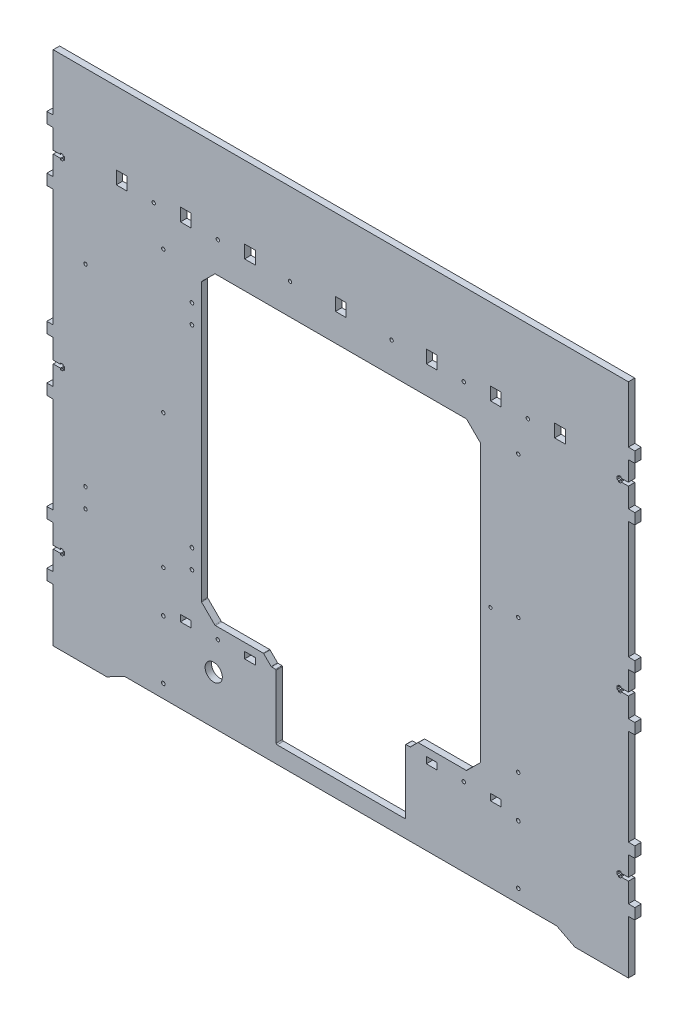
SolidWorks part; units mm, degrees
material "Клен"
ref_plane "Front" through (0, 0, 0) normal (0, 0, 1) x (1, 0, 0)
ref_plane "Top" through (0, 0, 0) normal (0, 1, 0) x (1, 0, 0)
ref_plane "Right" through (0, 0, 0) normal (1, 0, 0) x (0, 0, -1)
sketch "Эскиз2" plane through (0, 0, 0) normal (0, 0, 1) x (1, 0, 0)
  line L0 (400.4244, 482.0072) -> (-19.6784, 482.0072) construction
  line L1 (308.1919, 504.8221) -> (308.1919, 0) construction
  line L2 (39.1919, 504.8221) -> (39.1919, 18.7975) construction
  line L3 (33.1919, 504.8221) -> (33.1919, 18.7975) construction
  line L4 (228.1919, 149.8356) -> (228.1919, 102.1072) construction
  line L5 (168.1919, 135.3857) -> (168.1919, 108.8729) construction
  line L6 (193.1919, 141.9072) -> (193.1919, 108.8729) construction
  line L7 (260.6919, 457.1072) -> (260.6919, 439.2572) construction
  line L8 (228.1919, 461.9072) -> (228.1919, 439.2572) construction
  line L13 (193.1919, 457.1072) -> (193.1919, 440.4572) construction
  line L19 (39.1919, 472.1072) -> (33.1919, 472.0072)
  line L20 (33.1919, 472.0072) -> (33.1919, 462.0072)
  line L21 (33.1919, 462.0072) -> (39.1919, 461.9072)
  line L22 (39.1919, 461.9072) -> (39.1919, 443.5572)
  line L23 (39.1919, 443.5572) -> (45.9919, 443.5572)
  line L24 (45.9919, 443.5572) -> (45.9919, 444.7572)
  line L25 (45.9919, 444.7572) -> (48.1919, 444.7572)
  line L26 (48.1919, 444.7572) -> (48.1919, 443.5572)
  line L27 (48.1919, 443.5572) -> (49.6919, 443.5572)
  line L28 (49.6919, 443.5572) -> (49.6919, 440.4572)
  line L29 (49.6919, 440.4572) -> (48.1919, 440.4572)
  line L30 (48.1919, 440.4572) -> (48.1919, 439.2572)
  line L31 (48.1919, 439.2572) -> (45.9919, 439.2572)
  line L32 (45.9919, 439.2572) -> (45.9919, 440.4572)
  line L33 (45.9919, 440.4572) -> (39.1919, 440.4572)
  line L34 (39.1919, 440.4572) -> (39.1919, 422.1072)
  line L35 (39.1919, 422.1072) -> (33.1919, 422.0072)
  line L36 (33.1919, 422.0072) -> (33.1919, 412.0072)
  line L37 (33.1919, 412.0072) -> (39.1919, 411.9072)
  line L38 (39.1919, 411.9072) -> (39.1919, 302.1072)
  line L39 (39.1919, 302.1072) -> (33.1919, 302.0072)
  line L40 (33.1919, 302.0072) -> (33.1919, 292.0072)
  line L41 (33.1919, 292.0072) -> (39.1919, 291.9072)
  line L42 (39.1919, 291.9072) -> (39.1919, 273.5572)
  line L43 (39.1919, 273.5572) -> (45.9919, 273.5572)
  line L44 (45.9919, 273.5572) -> (45.9919, 274.7572)
  line L45 (45.9919, 274.7572) -> (48.1919, 274.7572)
  line L46 (48.1919, 274.7572) -> (48.1919, 273.5572)
  line L47 (48.1919, 273.5572) -> (49.6919, 273.5572)
  line L48 (49.6919, 273.5572) -> (49.6919, 270.4572)
  line L49 (49.6919, 270.4572) -> (48.1919, 270.4572)
  line L50 (48.1919, 270.4572) -> (48.1919, 269.2572)
  line L51 (48.1919, 269.2572) -> (45.9919, 269.2572)
  line L52 (45.9919, 269.2572) -> (45.9919, 270.4572)
  line L53 (45.9919, 270.4572) -> (39.1919, 270.4572)
  line L54 (39.1919, 270.4572) -> (39.1919, 252.1072)
  line L55 (39.1919, 252.1072) -> (33.1919, 252.0072)
  line L56 (33.1919, 252.0072) -> (33.1919, 242.0072)
  line L57 (33.1919, 242.0072) -> (39.1919, 241.9072)
  line L58 (39.1919, 241.9072) -> (39.1919, 152.1072)
  line L59 (39.1919, 152.1072) -> (33.1919, 152.0072)
  line L60 (33.1919, 152.0072) -> (33.1919, 142.0072)
  line L61 (33.1919, 142.0072) -> (39.1919, 141.9072)
  line L62 (39.1919, 141.9072) -> (39.1919, 123.5572)
  line L63 (39.1919, 123.5572) -> (45.9919, 123.5572)
  line L64 (45.9919, 123.5572) -> (45.9919, 124.7572)
  line L65 (45.9919, 124.7572) -> (48.1919, 124.7572)
  line L66 (48.1919, 124.7572) -> (48.1919, 123.5572)
  line L67 (48.1919, 123.5572) -> (49.6919, 123.5572)
  line L68 (49.6919, 123.5572) -> (49.6919, 120.4572)
  line L69 (49.6919, 120.4572) -> (48.1919, 120.4572)
  line L70 (48.1919, 120.4572) -> (48.1919, 119.2572)
  line L71 (48.1919, 119.2572) -> (45.9919, 119.2572)
  line L72 (45.9919, 119.2572) -> (45.9919, 120.4572)
  line L73 (45.9919, 120.4572) -> (39.1919, 120.4572)
  line L74 (39.1919, 120.4572) -> (39.1919, 102.1072)
  line L75 (39.1919, 102.1072) -> (33.1919, 102.0072)
  line L76 (33.1919, 102.0072) -> (33.1919, 92.0072)
  line L77 (33.1919, 92.0072) -> (39.1919, 91.9072)
  line L78 (39.1919, 91.9072) -> (39.1919, 42.0072)
  line L79 (39.1919, 42.0072) -> (89.1919, 42.0072)
  line L80 (89.1919, 42.0072) -> (106.1919, 50.7072)
  line L81 (106.1919, 50.7072) -> (510.1919, 50.7072)
  line L82 (313.1919, 457.1072) -> (303.1919, 457.1072)
  line L83 (168.1919, 461.9072) -> (168.1919, 439.2572) construction
  line L84 (303.1919, 457.1072) -> (303.1919, 445.0072)
  line L85 (303.1919, 445.0072) -> (313.1919, 445.0072)
  line L87 (169.3644, 152.1072) -> (169.3644, 392.271) construction
  line L88 (218.1919, 127.1049) -> (228.1919, 127.1049)
  line L89 (218.1919, 127.1049) -> (218.1919, 121.0049)
  line L90 (218.1919, 121.0049) -> (228.1919, 121.0049)
  line L91 (228.1919, 127.1049) -> (228.1919, 121.0049)
  line L92 (158.1919, 127.1049) -> (168.1919, 127.1049)
  line L93 (158.1919, 127.1049) -> (158.1919, 121.0049)
  line L94 (158.1919, 121.0049) -> (168.1919, 121.0049)
  line L95 (168.1919, 127.1049) -> (168.1919, 121.0049)
  line L96 (158.1919, 457.1072) -> (168.1919, 457.1072)
  line L97 (158.1919, 457.1072) -> (158.1919, 445.0072)
  line L98 (158.1919, 445.0072) -> (168.1919, 445.0072)
  line L99 (168.1919, 457.1072) -> (168.1919, 445.0072)
  line L100 (218.1919, 457.1072) -> (228.1919, 457.1072)
  line L101 (218.1919, 457.1072) -> (218.1919, 445.0072)
  line L102 (218.1919, 445.0072) -> (228.1919, 445.0072)
  line L103 (228.1919, 457.1072) -> (228.1919, 445.0072)
  line L105 (367.6919, 66.6049) -> (248.6919, 66.6049)
  line L107 (247.6919, 67.6049) -> (247.6919, 126.6049)
  line L108 (247.1919, 127.1049) -> (243.399, 127.1049)
  line L109 (239.5515, 130.7453) -> (243.0455, 127.2514)
  line L111 (239.5515, 130.7453) -> (236.0575, 134.2393)
  line L112 (213.3308, 134.3857) -> (235.704, 134.3857)
  line L113 (108.1919, 457.1072) -> (108.1919, 445.0072)
  line L114 (213.3308, 134.3857) -> (190.9576, 134.3857)
  line L115 (184.1064, 140.7795) -> (190.253, 134.6761)
  line L116 (98.1919, 445.0072) -> (108.1919, 445.0072)
  line L117 (184.1064, 140.7795) -> (177.9598, 146.8828)
  line L118 (177.6644, 169.7011) -> (177.6644, 147.5924)
  line L119 (98.1919, 457.1072) -> (108.1919, 457.1072)
  line L120 (177.6644, 169.7011) -> (177.6644, 405.9627)
  line L121 (184.1064, 412.7756) -> (177.9598, 406.6723)
  line L122 (98.1919, 457.1072) -> (98.1919, 445.0072)
  line L123 (184.1064, 412.7756) -> (190.253, 418.8789)
  line L124 (308.1379, 419.1693) -> (190.9576, 419.1693)
  line L125 (518.1919, 457.1072) -> (508.1919, 457.1072)
  line L126 (308.2459, 419.1693) -> (425.4263, 419.1693)
  line L127 (432.2775, 412.7756) -> (426.1309, 418.8789)
  line L128 (432.2775, 412.7756) -> (438.4241, 406.6723)
  line L129 (438.7195, 169.7011) -> (438.7195, 405.9627)
  line L130 (438.7195, 169.7011) -> (438.7195, 147.5924)
  line L131 (432.2775, 140.7795) -> (438.4241, 146.8828)
  line L132 (432.2775, 140.7795) -> (426.1309, 134.6761)
  line L133 (403.0531, 134.3857) -> (425.4263, 134.3857)
  line L134 (403.0531, 134.3857) -> (380.6799, 134.3857)
  line L135 (376.8323, 130.7453) -> (380.3263, 134.2393)
  line L136 (376.8323, 130.7453) -> (373.3384, 127.2514)
  line L137 (369.1919, 127.1049) -> (372.9848, 127.1049)
  line L138 (368.6919, 67.6049) -> (368.6919, 126.6049)
  line L139 (388.1919, 457.1072) -> (388.1919, 445.0072)
  line L140 (398.1919, 445.0072) -> (388.1919, 445.0072)
  line L141 (398.1919, 457.1072) -> (398.1919, 445.0072)
  line L142 (398.1919, 457.1072) -> (388.1919, 457.1072)
  line L143 (448.1919, 457.1072) -> (448.1919, 445.0072)
  line L144 (458.1919, 445.0072) -> (448.1919, 445.0072)
  line L145 (458.1919, 457.1072) -> (458.1919, 445.0072)
  line L146 (458.1919, 457.1072) -> (448.1919, 457.1072)
  line L147 (448.1919, 127.1049) -> (448.1919, 121.0049)
  line L148 (458.1919, 121.0049) -> (448.1919, 121.0049)
  line L149 (458.1919, 127.1049) -> (458.1919, 121.0049)
  line L150 (458.1919, 127.1049) -> (448.1919, 127.1049)
  line L151 (388.1919, 127.1049) -> (388.1919, 121.0049)
  line L152 (398.1919, 121.0049) -> (388.1919, 121.0049)
  line L153 (398.1919, 127.1049) -> (398.1919, 121.0049)
  line L154 (398.1919, 127.1049) -> (388.1919, 127.1049)
  line L155 (313.1919, 457.1072) -> (313.1919, 445.0072)
  line L156 (527.1919, 42.0072) -> (510.1919, 50.7072)
  line L157 (577.1919, 42.0072) -> (527.1919, 42.0072)
  line L158 (577.1919, 91.9072) -> (577.1919, 42.0072)
  line L159 (583.1919, 92.0072) -> (577.1919, 91.9072)
  line L160 (583.1919, 102.0072) -> (583.1919, 92.0072)
  line L161 (577.1919, 102.1072) -> (583.1919, 102.0072)
  line L162 (577.1919, 120.4572) -> (577.1919, 102.1072)
  line L163 (570.3919, 120.4572) -> (577.1919, 120.4572)
  line L164 (570.3919, 119.2572) -> (570.3919, 120.4572)
  line L165 (568.1919, 119.2572) -> (570.3919, 119.2572)
  line L166 (568.1919, 120.4572) -> (568.1919, 119.2572)
  line L167 (566.6919, 120.4572) -> (568.1919, 120.4572)
  line L168 (566.6919, 123.5572) -> (566.6919, 120.4572)
  line L169 (568.1919, 123.5572) -> (566.6919, 123.5572)
  line L170 (568.1919, 124.7572) -> (568.1919, 123.5572)
  line L171 (570.3919, 124.7572) -> (568.1919, 124.7572)
  line L172 (570.3919, 123.5572) -> (570.3919, 124.7572)
  line L173 (577.1919, 123.5572) -> (570.3919, 123.5572)
  line L174 (577.1919, 141.9072) -> (577.1919, 123.5572)
  line L175 (583.1919, 142.0072) -> (577.1919, 141.9072)
  line L176 (583.1919, 152.0072) -> (583.1919, 142.0072)
  line L177 (577.1919, 152.1072) -> (583.1919, 152.0072)
  line L178 (577.1919, 241.9072) -> (577.1919, 152.1072)
  line L179 (583.1919, 242.0072) -> (577.1919, 241.9072)
  line L180 (583.1919, 252.0072) -> (583.1919, 242.0072)
  line L181 (577.1919, 252.1072) -> (583.1919, 252.0072)
  line L182 (577.1919, 270.4572) -> (577.1919, 252.1072)
  line L183 (570.3919, 270.4572) -> (577.1919, 270.4572)
  line L184 (570.3919, 269.2572) -> (570.3919, 270.4572)
  line L185 (568.1919, 269.2572) -> (570.3919, 269.2572)
  line L186 (568.1919, 270.4572) -> (568.1919, 269.2572)
  line L187 (566.6919, 270.4572) -> (568.1919, 270.4572)
  line L188 (566.6919, 273.5572) -> (566.6919, 270.4572)
  line L189 (568.1919, 273.5572) -> (566.6919, 273.5572)
  line L190 (568.1919, 274.7572) -> (568.1919, 273.5572)
  line L191 (570.3919, 274.7572) -> (568.1919, 274.7572)
  line L192 (570.3919, 273.5572) -> (570.3919, 274.7572)
  line L193 (577.1919, 273.5572) -> (570.3919, 273.5572)
  line L194 (577.1919, 291.9072) -> (577.1919, 273.5572)
  line L195 (583.1919, 292.0072) -> (577.1919, 291.9072)
  line L196 (583.1919, 302.0072) -> (583.1919, 292.0072)
  line L197 (577.1919, 302.1072) -> (583.1919, 302.0072)
  line L198 (577.1919, 411.9072) -> (577.1919, 302.1072)
  line L199 (583.1919, 412.0072) -> (577.1919, 411.9072)
  line L200 (583.1919, 422.0072) -> (583.1919, 412.0072)
  line L201 (577.1919, 422.1072) -> (583.1919, 422.0072)
  line L202 (577.1919, 440.4572) -> (577.1919, 422.1072)
  line L203 (570.3919, 440.4572) -> (577.1919, 440.4572)
  line L204 (570.3919, 439.2572) -> (570.3919, 440.4572)
  line L205 (568.1919, 439.2572) -> (570.3919, 439.2572)
  line L206 (568.1919, 440.4572) -> (568.1919, 439.2572)
  line L207 (566.6919, 440.4572) -> (568.1919, 440.4572)
  line L208 (566.6919, 443.5572) -> (566.6919, 440.4572)
  line L209 (568.1919, 443.5572) -> (566.6919, 443.5572)
  line L210 (568.1919, 444.7572) -> (568.1919, 443.5572)
  line L211 (570.3919, 444.7572) -> (568.1919, 444.7572)
  line L212 (570.3919, 443.5572) -> (570.3919, 444.7572)
  line L213 (577.1919, 443.5572) -> (570.3919, 443.5572)
  line L214 (577.1919, 461.9072) -> (577.1919, 443.5572)
  line L215 (583.1919, 462.0072) -> (577.1919, 461.9072)
  line L216 (583.1919, 472.0072) -> (583.1919, 462.0072)
  line L217 (577.1919, 472.1072) -> (583.1919, 472.0072)
  line L226 (308.1379, 419.1693) -> (308.2459, 419.1693)
  line L227 (508.1919, 457.1072) -> (508.1919, 445.0072)
  line L228 (518.1919, 457.1072) -> (518.1919, 445.0072)
  line L229 (518.1919, 445.0072) -> (508.1919, 445.0072)
  line L230 (474.1919, 504.8221) -> (474.1919, 18.7975) construction
  line L231 (448.1919, 445.0072) -> (600.6121, 445.0072) construction
  line L232 (600.6121, 415.0072) -> (458.1919, 415.0072) construction
  line L233 (600.6121, 157.1049) -> (458.1919, 157.1049) construction
  line L234 (448.1919, 127.1049) -> (600.6121, 127.1049) construction
  line L235 (458.1919, 282.5072) -> (600.6121, 282.5072) construction
  line L236 (577.1919, 526.0504) -> (577.1919, 0) construction
  line L237 (604.7948, 525.0072) -> (26.3205, 525.0072) construction
  line L238 (39.1919, 472.1072) -> (39.1919, 525.0072)
  line L239 (39.1919, 525.0072) -> (577.1919, 525.0072)
  line L241 (577.1919, 525.0072) -> (577.1919, 472.1072)
  circle A4 centre (260.6919, 448.0572) radius 1.6
  circle A5 centre (193.1919, 448.0572) radius 1.6
  circle A7 centre (69.3644, 366.4593) radius 1.6
  circle A8 centre (69.3644, 186.0893) radius 1.6
  circle A9 centre (69.3644, 168.0893) radius 1.6
  circle A10 centre (193.1919, 124.0549) radius 1.6
  circle A11 centre (142.1919, 117.9049) radius 1.7
  circle A12 centre (142.1919, 63.1049) radius 1.7
  circle A13 centre (189.3045, 95.8269) radius 8.05
  arc A14 (248.6919, 66.6049) -> (247.6919, 67.6049) centre (248.6919, 67.6049) cw
  arc A15 (247.6919, 126.6049) -> (247.1919, 127.1049) centre (247.1919, 126.6049) ccw
  arc A16 (243.0455, 127.2514) -> (243.399, 127.1049) centre (243.399, 127.6049) ccw
  arc A17 (236.0575, 134.2393) -> (235.704, 134.3857) centre (235.704, 133.8857) ccw
  arc A18 (190.9576, 419.1693) -> (190.253, 418.8789) centre (190.9576, 418.1693) ccw
  arc A19 (177.9598, 406.6723) -> (177.6644, 405.9627) centre (178.6644, 405.9627) ccw
  arc A20 (177.9598, 146.8828) -> (177.6644, 147.5924) centre (178.6644, 147.5924) cw
  arc A21 (190.9576, 134.3857) -> (190.253, 134.6761) centre (190.9576, 135.3857) cw
  arc A22 (425.4263, 134.3857) -> (426.1309, 134.6761) centre (425.4263, 135.3857) ccw
  arc A23 (438.4241, 146.8828) -> (438.7195, 147.5924) centre (437.7195, 147.5924) ccw
  arc A24 (438.4241, 406.6723) -> (438.7195, 405.9627) centre (437.7195, 405.9627) cw
  arc A25 (425.4263, 419.1693) -> (426.1309, 418.8789) centre (425.4263, 418.1693) cw
  arc A26 (380.3263, 134.2393) -> (380.6799, 134.3857) centre (380.6799, 133.8857) cw
  arc A27 (373.3384, 127.2514) -> (372.9848, 127.1049) centre (372.9848, 127.6049) cw
  arc A28 (368.6919, 126.6049) -> (369.1919, 127.1049) centre (369.1919, 126.6049) cw
  arc A29 (367.6919, 66.6049) -> (368.6919, 67.6049) centre (367.6919, 67.6049) ccw
  circle A30 centre (474.1919, 63.1049) radius 1.7
  circle A31 centre (474.1919, 117.9049) radius 1.7
  circle A32 centre (423.1919, 124.0549) radius 1.6
  circle A33 centre (423.1919, 448.0572) radius 1.6
  circle A34 centre (355.6919, 448.0572) radius 1.6
  circle A35 centre (483.1919, 448.0572) radius 1.6
  circle A36 centre (133.1919, 448.0572) radius 1.6
  circle A37 centre (474.1919, 415.0072) radius 1.6
  circle A38 centre (474.1919, 282.5072) radius 1.6
  circle A39 centre (474.1919, 157.1049) radius 1.6
  circle A40 centre (142.1919, 157.1049) radius 1.6
  circle A41 centre (142.1919, 282.5072) radius 1.6
  circle A42 centre (142.1919, 415.0072) radius 1.6
  circle A43 centre (168.9644, 384.9627) radius 1.7
  circle A44 centre (168.9644, 366.9627) radius 1.7
  circle A45 centre (168.9644, 186.5924) radius 1.7
  circle A46 centre (168.9644, 168.5924) radius 1.7
  circle A47 centre (448.149, 277.6693) radius 1.5
  point P40 (577.1919, 357.0072)
  point P331 (308.1919, 66.6049)
  point P348 (308.1919, 445.0072)
  point P349 (308.1919, 457.1072)
  dimension "D3" = 103
  dimension "D4" = 30
  dimension "D5" = 1
  dimension "D6" = 0.5
  dimension "D7" = 0.5
  dimension "D8" = 0.5
  dimension "D9" = 1
  dimension "D10" = 1
  dimension "D11" = 1
  dimension "D12" = 1
  dimension "D15" = 58.3874
  dimension "D26" = 3.2
  dimension "D27" = 3.2
  dimension "D28" = 3.2
  dimension "D30" = 3
  dimension "D13" = 6
  dimension "D14" = 269
  dimension "D16" = 47.5
  dimension "D17" = 32.5
  dimension "D18" = 35
  dimension "D19" = 25
  dimension "D20" = 30
  dimension "D21" = 138.8276
  dimension "D22" = 80
  dimension "D23" = 35
  dimension "D24" = 25
  dimension "D25" = 162.5
  dimension "D29" = 269
extrude "Бобышка-Вытянуть2" add sketch "Эскиз2" along normal blind 6
